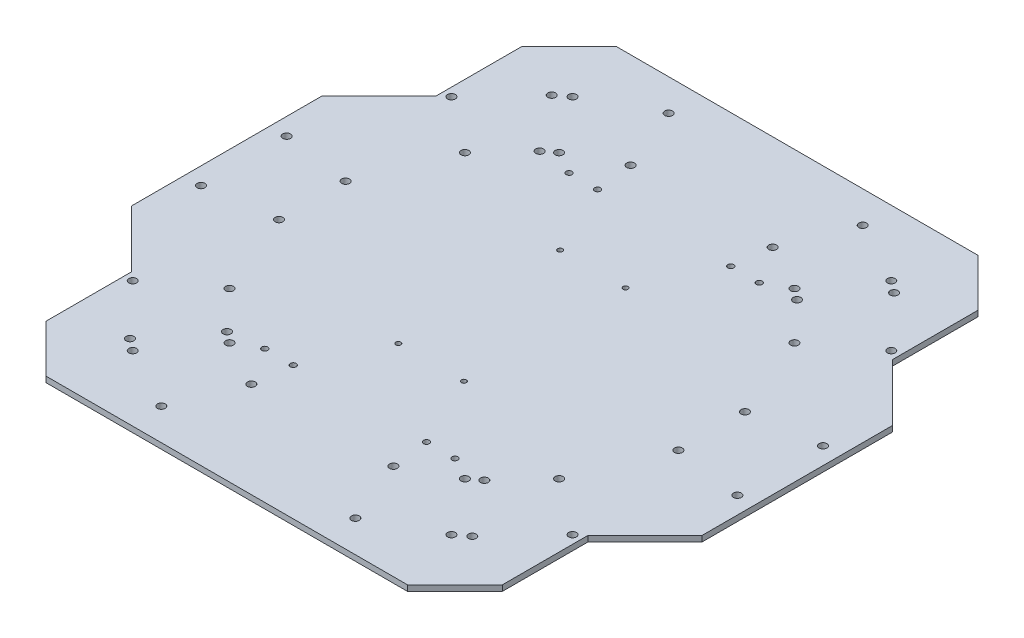
SolidWorks part; units mm, degrees
material "CF-ntbk"
ref_plane "Front Plane" through (0, 0, 0) normal (0, 0, 1) x (1, 0, 0)
ref_plane "Top Plane" through (0, 0, 0) normal (0, 1, 0) x (1, 0, 0)
ref_plane "Right Plane" through (0, 0, 0) normal (1, 0, 0) x (0, 0, -1)
sketch "Sketch1" plane through (0, 0, 0) normal (0, 1, 0) x (1, 0, 0)
  line L0 (-95, 150) -> (-120, 125)
  line L1 (-120, 125) -> (-120, 80)
  line L2 (-120, 80) -> (-150, 50)
  line L3 (-150, 50) -> (-150, -50)
  line L4 (-150, -50) -> (-120, -80)
  line L5 (-120, -80) -> (-120, -125)
  line L6 (-120, -125) -> (-95, -150)
  line L7 (-95, -150) -> (95, -150)
  line L8 (95, -150) -> (120, -125)
  line L9 (120, -125) -> (120, -80)
  line L10 (120, -80) -> (150, -50)
  line L11 (150, -50) -> (150, 50)
  line L12 (150, 50) -> (120, 80)
  line L13 (120, 80) -> (120, 125)
  line L14 (120, 125) -> (95, 150)
  line L15 (95, 150) -> (-95, 150)
  line L17 (-44.2539, 0) -> (44.2539, 0) construction
  line L18 (0, -44.7868) -> (0, 44.7868) construction
  dimension "D2" = 150
  dimension "D1" = 95
  dimension "D3" = 300
  dimension "D4" = 190
  dimension "D5" = 100
  dimension "D6" = 30
  dimension "D7" = 45
  dimension "D8" = 135
extrude "Boss-Extrude1" add sketch "Sketch1" along normal blind 3
sketch "Sketch2" plane through (0, 3, 0) normal (0, 1, 0) x (1, 0, 0)
  line L0 (-79.7985, -138.215) -> (79.7985, 138.215) construction
  line L1 (27.6134, 105.301) -> (76.8653, 76.8653) construction
  line L2 (-69.8318, 120.9522) -> (69.8318, -120.9522) construction
  line L3 (0, -44.7868) -> (0, 44.7868) construction
  line L5 (-44.2539, 0) -> (44.2539, 0) construction
  line L6 (-150.8166, 0) -> (150.8166, 0) construction
  line L7 (-118.217, -118.217) -> (118.217, 118.217) construction
  line L8 (-102.6144, 102.6144) -> (102.6144, -102.6144) construction
  line L9 (105, 17.5) -> (105, -25.4677) construction
  line L11 (30.9172, -103.3935) -> (75.1288, -77.8679) construction
  circle A0 centre (51.0144, 133.3596) radius 2.05
  circle A1 centre (37.3446, 99.6827) radius 2.05
  circle A2 centre (37.3446, -99.6827) radius 2.05
  circle A3 centre (51.0144, -133.3596) radius 2.05
  circle A4 centre (105, 17.5) radius 2.05
  circle A5 centre (141, 22.5) radius 2.05
  circle A12 centre (105, -17.5) radius 2.05
  circle A13 centre (141, -22.5) radius 2.05
  circle A16 centre (89.9856, -110.8596) radius 2.05
  circle A17 centre (67.6554, -82.1827) radius 2.05
  circle A18 centre (89.9856, 110.8596) radius 2.05
  circle A19 centre (67.6554, 82.1827) radius 2.05
  dimension "D1" = 4.1
  dimension "D3" = 30
  dimension "D5" = 30
  dimension "D10" = 45
  dimension "D11" = 45
  dimension "D4" = 17.5
  dimension "D7" = 105
  dimension "D15" = 105
  dimension "D17" = 105
  dimension "D20" = 17.5
  dimension "D24" = 17.5
  dimension "D29" = 17.5
  dimension "D12" = 17.5
  dimension "D16" = 17.5
  dimension "D9" = 22.5
  dimension "D22" = 22.5
  dimension "D23" = 36
  dimension "D26" = 36
  dimension "D8" = 22.5
  dimension "D13" = 22.5
  dimension "D14" = 36
  dimension "D21" = 36
  dimension "D6" = 22.5
  dimension "D18" = 22.5
  dimension "D19" = 36
  dimension "D25" = 36
extrude "HexCut1" cut sketch "Sketch2" against normal up to surface (3 mm away) up to face at (0, 0, 0)
mirror "HexCut2" about plane through (0, 0, 0) normal (1, 0, 0) of "HexCut1"
sketch "ConstructLines" plane through (0, 3, 0) normal (0, 1, 0) x (1, 0, 0)
  line L0 (0, 121.6855) -> (0, -121.6855) construction
  line L1 (-91.1915, 0) -> (91.1915, 0) construction
  line L2 (-44.2539, 0) -> (44.2539, 0) construction
ref_point "Point1"
sketch "Sketch5" plane through (0, 3, 0) normal (0, 1, 0) x (1, 0, 0)
  line L0 (0, 121.6855) -> (0, -121.6855) construction
  line L1 (-91.1915, 0) -> (91.1915, 0) construction
  circle A0 centre (35, 80) radius 1.55
  circle A1 centre (50, 80) radius 1.55
  dimension "D1" = 3.1
  dimension "D2" = 15
  dimension "D3" = 35
  dimension "D4" = 80
extrude "Cut-Extrude2" cut sketch "Sketch5" against normal up to surface (3 mm away) up to face at (-51.0144, 0, -131.3096)
pattern_linear "LPattern1" count 2 spacing 160 along (0, 0, 1) count 2 spacing 85 along (-1, 0, 0) of "Cut-Extrude2"
sketch "Sketch6" plane through (0, 3, 0) normal (0, 1, 0) x (1, 0, 0)
  line L0 (-103.0997, -103.0997) -> (103.0997, 103.0997) construction
  line L1 (0, 121.6855) -> (0, -121.6855) construction
  line L2 (69.8057, 78.6867) -> (81.2763, 67.2162) construction
  line L3 (-98.3117, 98.3117) -> (98.3117, -98.3117) construction
  line L4 (83.4139, -65.0786) -> (62.2362, -86.2562) construction
  circle A0 centre (86.6206, 61.8718) radius 2.05
  circle A1 centre (115.612, 83.7922) radius 2.05
  circle A2 centre (83.7922, 115.612) radius 2.05
  circle A3 centre (61.8718, 86.6206) radius 2.05
  circle A4 centre (86.6206, -61.8718) radius 2.05
  circle A5 centre (61.8718, -86.6206) radius 2.05
  circle A6 centre (83.7922, -115.612) radius 2.05
  circle A7 centre (115.612, -83.7922) radius 2.05
  dimension "D13" = 22.5
  dimension "D14" = 36
  dimension "D6" = 22.5
  dimension "D4" = 4.1
  dimension "D1" = 45
  dimension "D2" = 105
  dimension "D5" = 17.5
  dimension "D7" = 17.5
  dimension "D10" = 105
  dimension "D11" = 17.5
  dimension "D15" = 17.5
  dimension "D17" = 45
  dimension "D3" = 22.5
  dimension "D8" = 36
  dimension "D9" = 36
  dimension "D12" = 22.5
  dimension "D16" = 36
extrude "QuadCut1" cut sketch "Sketch6" against normal up to surface (3 mm away) up to face at (50, 0, 81.55)
mirror "QuadCut2" about plane through (0, 0, 0) normal (1, 0, 0) of "QuadCut1"
sketch "Sketch7" plane through (0, 3, 0) normal (0, 1, 0) x (1, 0, 0)
  line L0 (0, -44.7868) -> (0, 44.7868) construction
  line L1 (-44.2539, 0) -> (44.2539, 0) construction
  circle A0 centre (-17.2, 42.5) radius 1.3
  circle A1 centre (17.2, 42.5) radius 1.3
  circle A2 centre (-17.2, -42.5) radius 1.3
  circle A3 centre (17.2, -42.5) radius 1.3
  dimension "D1" = 2.6
  dimension "D2" = 85
  dimension "D3" = 34.4
  dimension "D4" = 17.2
  dimension "D5" = 42.5
extrude "StdCarrierCubeFP" cut sketch "Sketch7" against normal up to surface (3 mm away) up to face at (-115.612, 0, 85.8422)
sketch "CubeJetsonSuit" plane through (0, 3, 0) normal (0, 1, 0) x (1, 0, 0)
  line L0 (-44.2539, 0) -> (44.2539, 0) construction
  line L1 (-40, 57.5) -> (40, 57.5)
  line L2 (-40, 57.5) -> (-40, -57.5)
  line L3 (-40, -57.5) -> (40, -57.5)
  line L4 (40, 57.5) -> (40, -57.5)
  line L5 (0, -44.7868) -> (0, 44.7868) construction
  dimension "D1" = 115
  dimension "D2" = 57.5
  dimension "D3" = 80
  dimension "D4" = 40
sketch "RPi4B" plane through (0, 3, 0) normal (0, 1, 0) x (1, 0, 0)
  line L0 (0, -44.7868) -> (0, 44.7868) construction
  line L1 (-28, 145) -> (28, 145)
  line L2 (-28, 145) -> (-28, 60)
  line L3 (-28, 60) -> (28, 60)
  line L4 (28, 145) -> (28, 60)
  line L6 (95, 150) -> (-95, 150) construction
  line L7 (-44.2539, 0) -> (44.2539, 0) construction
  line L8 (-95.6266, 42.5) -> (-39.6266, 42.5)
  line L9 (-95.6266, 42.5) -> (-95.6266, -42.5)
  line L10 (-95.6266, -42.5) -> (-39.6266, -42.5)
  line L11 (-39.6266, 42.5) -> (-39.6266, -42.5)
  dimension "D1" = 56
  dimension "D2" = 28
  dimension "D3" = 85
  dimension "D4" = 5
  dimension "D5" = 56
  dimension "D6" = 85
  dimension "D7" = 42.5
sketch "StdCubeCarrier" plane through (0, 3, 0) normal (0, 1, 0) x (1, 0, 0)
  line L0 (-44.2539, 0) -> (44.2539, 0) construction
  line L1 (-22.145, 47.23) -> (22.145, 47.23)
  line L2 (-22.145, 47.23) -> (-22.145, -47.23)
  line L3 (-22.145, -47.23) -> (22.145, -47.23)
  line L4 (22.145, 47.23) -> (22.145, -47.23)
  line L5 (0, -44.7868) -> (0, 44.7868) construction
  dimension "D1" = 94.46
  dimension "D2" = 47.23
  dimension "D3" = 44.29
  dimension "D4" = 22.145
sketch "JetsonNanoDev" plane through (0, 3, 0) normal (0, 1, 0) x (1, 0, 0)
  line L0 (-44.2539, 0) -> (44.2539, 0) construction
  line L1 (30.1184, 50) -> (110.1184, 50)
  line L2 (30.1184, 50) -> (30.1184, -50)
  line L3 (30.1184, -50) -> (110.1184, -50)
  line L4 (110.1184, 50) -> (110.1184, -50)
  dimension "D1" = 80
  dimension "D2" = 100
  dimension "D3" = 50
equation "\"ClampHoleDist\"= 36"
equation "\"ClampDistMid\"=105"
equation "\"Length\"= 300"
equation "\"D3@Sketch1\"=\"Length\""
equation "\"Width\"= 190"
equation "\"D1@Sketch1\"=\"Width\"/2"
equation "\"D2@Sketch1\"=\"Length\"/2"
equation "\"D4@Sketch1\"=\"Width\""
equation "\"D7@Sketch1\"=(\"Length\"- 210)/2"
equation "\"HoleZDist\"=80"
equation "\"D4@Sketch5\"=\"HoleZDist\""
equation "\"HoleXDist\"=35"
equation "\"D3@Sketch5\"=\"HoleXDist\""
equation "\"HoleSpacing\"=15"
equation "\"D2@Sketch5\"=\"HoleSpacing\""
equation "\"D3@LPattern1\"=\"HoleZDist\"*2"
equation "\"D4@LPattern1\"=\"HoleXDist\"*2+(\"HoleSpacing\")"
equation "\"ClampHoriDist\"=17.5"
equation "\"D4@Sketch2\"=\"ClampHoriDist\""
equation "\"D7@Sketch2\"=\"ClampDistMid\""
equation "\"D15@Sketch2\"=\"ClampDistMid\""
equation "\"D17@Sketch2\"=\"ClampDistMid\""
equation "\"D20@Sketch2\"=\"ClampHoriDist\""
equation "\"D24@Sketch2\"=\"ClampHoriDist\""
equation "\"D29@Sketch2\"=\"ClampHoriDist\""
equation "\"D12@Sketch2\"=\"ClampHoriDist\""
equation "\"ClampHoleSize\"=4.1"
equation "\"D1@Sketch2\"=\"ClampHoleSize\""
equation "\"D16@Sketch2\"=\"ClampHoriDist\""
equation "\"D2@Sketch6\"=\"ClampDistMid\""
equation "\"D4@Sketch6\"=\"ClampHoleSize\""
equation "\"D5@Sketch6\"=\"ClampHoriDist\""
equation "\"D7@Sketch6\"=\"ClampHoriDist\""
equation "\"D10@Sketch6\"=\"ClampDistMid\""
equation "\"D11@Sketch6\"=\"ClampHoriDist\""
equation "\"D15@Sketch6\"=\"ClampHoriDist\""
equation "\"FrontClampHoriDist\"=22.5"
equation "\"D9@Sketch2\"=\"FrontClampHoriDist\""
equation "\"D22@Sketch2\"=\"FrontClampHoriDist\""
equation "\"D23@Sketch2\"=\"ClampHoleDist\""
equation "\"D26@Sketch2\"=\"ClampHoleDist\""
equation "\"D8@Sketch2\"=\"FrontClampHoriDist\""
equation "\"D13@Sketch2\"=\"FrontClampHoriDist\""
equation "\"D14@Sketch2\"=\"ClampHoleDist\""
equation "\"D21@Sketch2\"=\"ClampHoleDist\""
equation "\"D6@Sketch2\"=\"FrontClampHoriDist\""
equation "\"D18@Sketch2\"=\"FrontClampHoriDist\""
equation "\"D19@Sketch2\"=\"ClampHoleDist\""
equation "\"D25@Sketch2\"=\"ClampHoleDist\""
equation "\"D3@Sketch6\"=\"FrontClampHoriDist\""
equation "\"D6@Sketch6\"=\"FrontClampHoriDist\""
equation "\"D8@Sketch6\"=\"ClampHoleDist\""
equation "\"D9@Sketch6\"=\"ClampHoleDist\""
equation "\"D12@Sketch6\"=\"FrontClampHoriDist\""
equation "\"D13@Sketch6\"=\"FrontClampHoriDist\""
equation "\"D14@Sketch6\"=\"ClampHoleDist\""
equation "\"D16@Sketch6\"=\"ClampHoleDist\""
